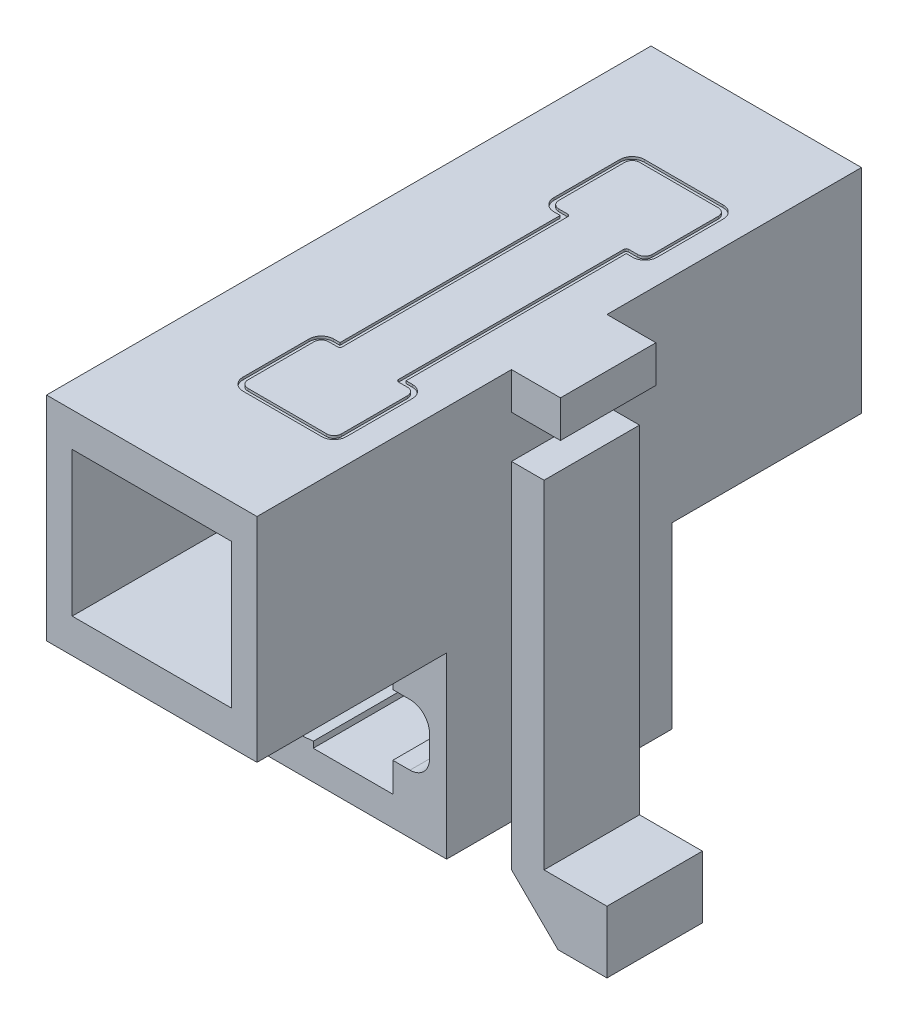
SolidWorks part; units mm, degrees
ref_plane "Front Plane" through (0, 0, 0) normal (0, 0, 1) x (1, 0, 0)
ref_plane "Top Plane" through (0, 0, 0) normal (0, 1, 0) x (1, 0, 0)
ref_plane "Right Plane" through (0, 0, 0) normal (1, 0, 0) x (0, 0, -1)
sketch "Sketch1" plane through (0, 0, 0) normal (0, 0, 1) x (1, 0, 0)
  line L1 (-4.3, 4.35) -> (4.3, 4.35)
  line L2 (-4.3, 4.35) -> (-4.3, -4.35)
  line L3 (-4.3, -4.35) -> (4.3, -4.35)
  line L4 (4.3, 4.35) -> (4.3, -4.35)
  line L5 (-3.25, 2.95) -> (3.25, 2.95)
  line L6 (-3.25, 2.95) -> (-3.25, -2.95)
  line L7 (-3.25, -2.95) -> (3.25, -2.95)
  line L8 (3.25, 2.95) -> (3.25, -2.95)
  dimension "D1" = 8.7
  dimension "D2" = 8.6
  dimension "D3" = 1.4
  dimension "D4" = 1.4
  dimension "D5" = 1.05
  dimension "D6" = 1.05
  dimension "D7" = 4.3
  dimension "D8" = 4.35
extrude "Boss-Extrude1" add sketch "Sketch1" along normal blind 24.7
ref_plane "Plane1" through (0, 0, 12.35) normal (0, 0, 1) x (1, 0, 0)
sketch "Sketch2" plane through (0, 0, 12.35) normal (0, 0, 1) x (1, 0, 0)
  line L0 (4.3, -4.35) -> (4.3, 4.35) construction
  line L1 (4.3, 4.35) -> (6.3, 4.35) construction
  line L2 (4.3, 4.35) -> (4.3, 2.84)
  line L3 (4.3, 2.84) -> (6.3, 2.84)
  line L4 (6.3, 4.35) -> (6.3, 2.84)
  line L5 (4.3, 1.1) -> (5.63, 1.1)
  line L6 (4.3, 1.1) -> (4.3, -13.35)
  line L8 (5.63, 1.1) -> (5.63, -12.69)
  line L9 (4.3, -13.35) -> (6.2, -15.23)
  line L10 (6.2, -15.23) -> (8.2, -15.23)
  line L12 (5.63, -12.69) -> (8.2, -12.69)
  line L13 (8.2, -15.23) -> (8.2, -12.69)
  line L14 (4.3, 4.35) -> (-4.3, 4.35) construction
  line L15 (-4.3, -4.35) -> (4.3, -4.35) construction
  line L16 (4.3, 4.35) -> (-4.3, 4.35) construction
  line L17 (4.3, 4.35) -> (6.3, 4.35)
  dimension "D1" = 1.51
  dimension "D2" = 1.33
  dimension "D3" = 3.9
  dimension "D4" = 2.54
  dimension "D5" = 19.58
  dimension "D6" = 2
  dimension "D7" = 9
  dimension "D8" = 3.25
  dimension "D9" = 2
extrude "Boss-Extrude2" add sketch "Sketch2" along normal blind 1.95 and the other way blind 1.95
sketch "Sketch3" plane through (0, 0, 12.35) normal (0, 0, 1) x (1, 0, 0)
  line L0 (4.3, -4.35) -> (4.3, -13.35) construction
  line L1 (-4.3, -4.35) -> (4.3, -4.35)
  line L2 (-4.3, -4.35) -> (-4.3, -11.65)
  line L3 (-4.3, -11.65) -> (4.3, -11.65)
  line L4 (4.3, -4.35) -> (4.3, -11.65)
  line L5 (4.3, 4.35) -> (-4.3, 4.35) construction
  line L6 (-4.3, -5.55) -> (-1.15, -5.8)
  line L7 (-1.15, -5.55) -> (2.1, -5.55)
  line L8 (-4.3, -5.55) -> (-4.3, -10.45)
  line L9 (-1.15, -10.45) -> (2.1, -10.45)
  line L10 (2.1, -5.55) -> (2.1, -6.75)
  line L11 (-1.15, -5.8) -> (-1.15, -5.55)
  line L12 (-4.3, -10.45) -> (-1.15, -10.2)
  line L13 (-1.15, -10.2) -> (-1.15, -10.45)
  line L14 (2.1, -9.25) -> (2.1, -10.45)
  line L15 (2.1, -6.75) -> (2.8, -6.75)
  line L17 (2.1, -9.25) -> (2.8, -9.25)
  line L18 (3.6, -7.55) -> (3.6, -8.45)
  arc A0 (2.8, -9.25) -> (3.6, -8.45) centre (2.8, -8.45) ccw
  arc A1 (2.8, -6.75) -> (3.6, -7.55) centre (2.8, -7.55) cw
  point P13 (-1.15, -10.325)
  point P24 (3.6, -9.25)
  point P27 (3.6, -6.75)
  dimension "D12" = 0.8
  dimension "D1" = 16
  dimension "D2" = 1.2
  dimension "D3" = 1.2
  dimension "D4" = 6.4
  dimension "D5" = 3.15
  dimension "D6" = 1.45
  dimension "D7" = 1.45
  dimension "D8" = 2.5
  dimension "D9" = 1.5
  dimension "D10" = 4.9
  dimension "D11" = 1.2
  dimension "D13" = 3.6
  dimension "D14" = 4.35
  dimension "D15" = 11.65
  dimension "D16" = 5.55
extrude "Boss-Extrude3" add sketch "Sketch3" along normal blind 4.6 and the other way blind 4.6 contours L15 A1 L18 A0 L17 L14 L9 L13 L12 L2 L3 L4 L1 L6 L11 L7 L10 region at (0, -4.4628, 12.35)
sketch "Sketch4" plane through (0, 4.35, 0) normal (0, 1, 0) x (1, 0, 0)
  line L0 (-0.16, -12.35) -> (-0.16, -16.85)
  line L9 (-6.875, -12.35) -> (6.875, -12.35) construction
  line L10 (-0.16, -16.85) -> (-0.42, -16.85)
  line L11 (-0.42, -20.55) -> (2.8, -20.55)
  line L12 (2.8, -16.85) -> (2.54, -16.85)
  line L13 (2.54, -16.85) -> (2.54, -12.35)
  line L14 (-0.92, -20.05) -> (-0.92, -17.35)
  line L15 (3.3, -20.05) -> (3.3, -17.35)
  line L16 (4.3, -24.7) -> (4.3, -14.3) construction
  line L19 (4.3, 0) -> (-4.3, 0) construction
  line L20 (2.34, -16.95) -> (2.34, -7.75)
  line L21 (2.8, -17.05) -> (2.44, -17.05)
  line L22 (3.1, -20.05) -> (3.1, -17.35)
  line L23 (-0.42, -20.35) -> (2.8, -20.35)
  line L24 (-0.72, -20.05) -> (-0.72, -17.35)
  line L25 (-0.06, -17.05) -> (-0.42, -17.05)
  line L26 (0.04, -7.75) -> (0.04, -16.95)
  line L27 (2.34, -17.05) -> (2.34, -12.35) construction
  line L28 (2.8, -17.05) -> (2.34, -17.05) construction
  line L29 (0.04, -17.05) -> (-0.42, -17.05) construction
  line L30 (0.04, -12.35) -> (0.04, -17.05) construction
  line L31 (-5.2058, -12.35) -> (9.2224, -12.35) construction
  line L32 (-0.06, -7.65) -> (-0.42, -7.65)
  line L33 (-0.72, -4.65) -> (-0.72, -7.35)
  line L34 (-0.42, -4.35) -> (2.8, -4.35)
  line L35 (3.1, -4.65) -> (3.1, -7.35)
  line L36 (2.8, -7.65) -> (2.44, -7.65)
  line L37 (3.3, -4.65) -> (3.3, -7.35)
  line L38 (-0.92, -4.65) -> (-0.92, -7.35)
  line L39 (2.54, -7.85) -> (2.54, -12.35)
  line L40 (2.8, -7.85) -> (2.54, -7.85)
  line L41 (-0.42, -4.15) -> (2.8, -4.15)
  line L42 (-0.16, -7.85) -> (-0.42, -7.85)
  line L43 (-0.16, -12.35) -> (-0.16, -7.85)
  arc A0 (-0.42, -16.85) -> (-0.92, -17.35) centre (-0.42, -17.35) ccw
  arc A1 (3.3, -17.35) -> (2.8, -16.85) centre (2.8, -17.35) ccw
  arc A2 (2.8, -20.55) -> (3.3, -20.05) centre (2.8, -20.05) ccw
  arc A3 (-0.92, -20.05) -> (-0.42, -20.55) centre (-0.42, -20.05) ccw
  arc A4 (3.1, -17.35) -> (2.8, -17.05) centre (2.8, -17.35) ccw
  arc A5 (2.8, -20.35) -> (3.1, -20.05) centre (2.8, -20.05) ccw
  arc A6 (-0.72, -20.05) -> (-0.42, -20.35) centre (-0.42, -20.05) ccw
  arc A7 (-0.42, -17.05) -> (-0.72, -17.35) centre (-0.42, -17.35) ccw
  arc A8 (2.34, -16.95) -> (2.44, -17.05) centre (2.44, -16.95) ccw
  arc A9 (-0.06, -17.05) -> (0.04, -16.95) centre (-0.06, -16.95) ccw
  arc A10 (-0.06, -7.65) -> (0.04, -7.75) centre (-0.06, -7.75) cw
  arc A11 (2.34, -7.75) -> (2.44, -7.65) centre (2.44, -7.75) cw
  arc A12 (-0.42, -7.65) -> (-0.72, -7.35) centre (-0.42, -7.35) cw
  arc A13 (-0.72, -4.65) -> (-0.42, -4.35) centre (-0.42, -4.65) cw
  arc A14 (2.8, -4.35) -> (3.1, -4.65) centre (2.8, -4.65) cw
  arc A15 (3.1, -7.35) -> (2.8, -7.65) centre (2.8, -7.35) cw
  arc A16 (-0.92, -4.65) -> (-0.42, -4.15) centre (-0.42, -4.65) cw
  arc A17 (2.8, -4.15) -> (3.3, -4.65) centre (2.8, -4.65) cw
  arc A18 (3.3, -7.35) -> (2.8, -7.85) centre (2.8, -7.35) cw
  arc A19 (-0.42, -7.85) -> (-0.92, -7.35) centre (-0.42, -7.35) cw
  point P8 (-0.92, -4.15)
  point P17 (-0.92, -16.85)
  point P22 (3.3, -20.55)
  point P25 (-0.92, -20.55)
  point P70 (3.3, -4.15)
  point P84 (-0.92, -7.85)
  dimension "D9" = 0.5
  dimension "D11" = 0.1
  dimension "D1" = 4.22
  dimension "D2" = 2.7
  dimension "D3" = 3.7
  dimension "D4" = 0.76
  dimension "D5" = 1
  dimension "D6" = 0.76
  dimension "D7" = 8.2
  dimension "D8" = 16.85
extrude "Cut-Extrude1" cut sketch "Sketch4" against normal blind 0.1
equation "\"D7@Sketch1\"=\"D2@Sketch1\"/2"
equation "\"D8@Sketch1\"=\"D1@Sketch1\"/2"
equation "\"D11@Sketch3\"=(\"D10@Sketch3\"-\"D8@Sketch3\")/2"
equation "\"D4@Sketch4\"=(\"D1@Sketch4\"-\"D2@Sketch4\")/2"
